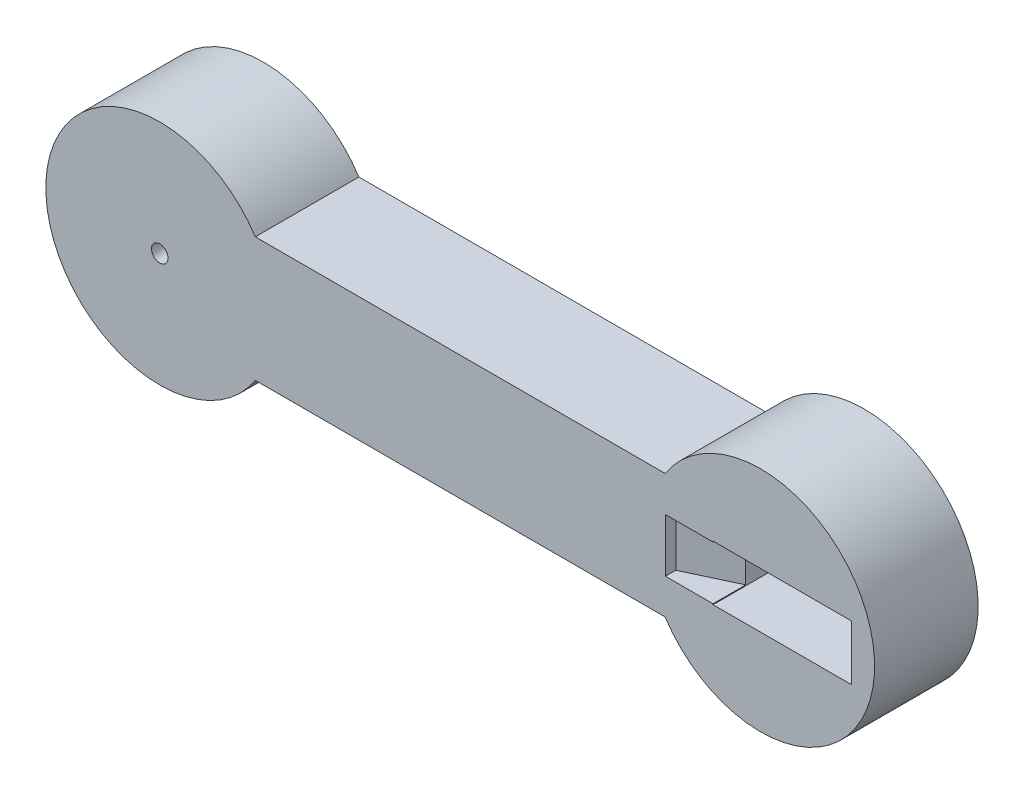
SolidWorks part; units mm, degrees
material "Custom Plastic"
ref_plane "Front Plane" through (0, 0, 0) normal (0, 0, 1) x (1, 0, 0)
ref_plane "Top Plane" through (0, 0, 0) normal (0, 1, 0) x (1, 0, 0)
ref_plane "Right Plane" through (0, 0, 0) normal (1, 0, 0) x (0, 0, -1)
sketch "Sketch1" plane through (0, 0, 0) normal (0, 0, 1) x (1, 0, 0)
  line L1 (0, 15) -> (145, 15)
  line L2 (0, 15) -> (0, -15)
  line L3 (0, -15) -> (145, -15)
  line L4 (145, 15) -> (145, -15)
  circle A0 centre (0, 0) radius 27.5
  circle A1 centre (145, 0) radius 27.5
  circle A2 centre (0, 0) radius 20
  point P9 (0, 0)
  dimension "D1" = 55
  dimension "D4" = 55
  dimension "D5" = 40
  dimension "D2" = 145
  dimension "D3" = 30
extrude "Boss-Extrude1" add sketch "Sketch1" along normal blind 25 contours L3 A1 L1 L4 | A1 L1 A0 L3 | L1 A1 L3 L4 | A2 L3 A0 L1 | A2 L1 A0 L3 | L3 A2 L1 L2 | L1 A2 L3 L2 region at (-6.7804, 0, 0) region at (9.0671, 0, 0) region at (-20.747, 0, 0) region at (21.8665, 0, 0) region at (72.5, 0, 0) region at (151.4116, 0, 0) region at (131.9332, 0, 0)
sketch "Sketch16" plane through (0, 0, 0) normal (0, 0, -1) x (-1, 0, 0)
  line L0 (-121.9511, -15) -> (-133.5193, -6.65) construction
  line L1 (-133.5193, -6.65) -> (-166.9193, -6.65)
  line L2 (-133.5193, -6.65) -> (-133.5193, 6.65)
  line L3 (-133.5193, 6.65) -> (-166.9193, 6.65)
  line L4 (-166.9193, -6.65) -> (-166.9193, 6.65)
  line L5 (-23.0489, -15) -> (-121.9511, -15) construction
  line L7 (-133.5193, 6.65) -> (-121.9511, 15) construction
  arc A1 (-121.9511, 15) -> (-121.9511, -15) centre (-145, 0) ccw construction
  dimension "D1" = 11.5682
  dimension "D2" = 33.4
  dimension "D3" = 13.3
extrude "Cut-Extrude10" cut sketch "Sketch16" against normal blind 4.5
ref_plane "Plane1" through (0, 0, 0) normal (0, -1, 0) x (-1, 0, 0)
sketch "Sketch19" plane through (0, 0, 0) normal (0, 0, -1) x (-1, 0, 0)
  circle A0 centre (0, 0) radius 20
extrude "Cut-Extrude14" cut sketch "Sketch19" against normal blind 5 contours A0
ref_plane "Plane2" through (0, 0, 6.5) normal (0, 0, -1) x (-1, 0, 0)
sketch "Sketch17" plane through (0, 0, 0) normal (0, 0, -1) x (-1, 0, 0)
  line L1 (-162.4193, 6.65) -> (-138.0193, 6.65)
  line L2 (-162.4193, 6.65) -> (-162.4193, -6.65)
  line L3 (-162.4193, -6.65) -> (-138.0193, -6.65)
  line L4 (-133.5193, -6.65) -> (-133.5193, 6.65)
  line L5 (-133.5193, 6.65) -> (-166.9193, 6.65)
  line L7 (-166.9193, -6.65) -> (-133.5193, -6.65)
  line L8 (-133.5193, -6.65) -> (-133.5193, 6.65)
  line L9 (-133.5193, 6.65) -> (-166.9193, 6.65)
  line L11 (-166.9193, -6.65) -> (-133.5193, -6.65)
  line L12 (-138.0193, 6.65) -> (-138.0193, -6.65)
  line L15 (-166.9193, 6.65) -> (-166.9193, -6.65)
  line L17 (-166.9193, 6.65) -> (-166.9193, -6.65)
  line M9 (-166.9193, 6.65) -> (-133.5193, 6.65)
  line M11 (-133.5193, -6.65) -> (-166.9193, -6.65)
  dimension "D2" = 4.5
  dimension "D3" = 4.5
  dimension "D1" = 0
extrude "Cut-Extrude11" cut sketch "Sketch17" against normal through all contours L12 L2 M9 M11 region at (150.2193, 0, 0)
sketch "Sketch18" plane through (0, 0, 0) normal (0, -1, 0) x (-1, 0, 0)
  line L0 (-138.0193, -25) -> (-138.0193, -15)
  line L6 (-122.0193, -25) -> (-122.0193, -22.5)
  line L8 (-166.9193, -4.5) -> (-162.4193, -4.5)
  line L9 (-166.9193, 0) -> (-166.9193, -4.5)
  line L11 (-166.9193, 0) -> (-166.9193, -4.5)
  line L13 (-133.5193, -4.5) -> (-133.5193, 0)
  line L14 (-133.5193, 0) -> (-166.9193, 0)
  line L16 (-166.9193, -4.5) -> (-162.4193, -4.5)
  line L21 (-133.5193, -4.5) -> (-133.5193, 0)
  line L22 (-133.5193, 0) -> (-166.9193, 0)
  line L26 (-122.0193, -22.5) -> (-138.0193, -15)
  line L28 (-23.0489, -25) -> (-121.9511, -25) construction
  line L30 (-138.0193, -25) -> (-122.0193, -25)
  line L31 (-138.0193, -15) -> (-138.0193, -25)
  line L34 (-162.4193, -25) -> (-138.0193, -25)
  line L35 (-162.4193, -25) -> (-138.0193, -25)
  line L36 (-138.0193, -25) -> (-138.0193, -4.5)
  line L37 (-138.0193, -25) -> (-138.0193, -4.5)
  line L38 (-162.4193, -4.5) -> (-162.4193, -25)
  line L40 (-162.4193, -4.5) -> (-162.4193, -25)
  line L42 (-138.0193, -4.5) -> (-133.5193, -4.5)
  line L43 (-138.0193, -4.5) -> (-133.5193, -4.5)
  dimension "D2" = 15
  dimension "D3" = 16
  dimension "D4" = 2.5
  dimension "D1" = 0
extrude "Cut-Extrude13" cut sketch "Sketch18" against normal mid plane 12.9 contours L0 region at (131.6193, 0, 21.5)
sketch "Sketch20" plane through (0, 0, 6.5) normal (0, 0, -1) x (-1, 0, 0)
  line L0 (-133.5193, 6.65) -> (-166.9193, 6.65) construction
  line L1 (-166.9193, 6.65) -> (-133.5193, 6.65)
  line L2 (-166.9193, 6.65) -> (-166.9193, -6.65)
  line L3 (-166.9193, -6.65) -> (-133.5193, -6.65)
  line L4 (-133.5193, 6.65) -> (-133.5193, -6.65)
  line L5 (-166.9193, 6.65) -> (-166.9193, -6.65) construction
  line L6 (-166.9193, -6.65) -> (-133.5193, -6.65) construction
  dimension "D1" = 33.4
extrude "Cut-Extrude15" cut sketch "Sketch20" against normal through all
sketch "Sketch21" plane through (0, 0, 0) normal (0, 0, -1) x (-1, 0, 0)
  circle A0 centre (-136.25, 0) radius 1.1
  circle A1 centre (-164.25, 0) radius 1.1
  dimension "D3" = 2.2
  dimension "D1" = 14.2989
  dimension "D2" = 28
extrude "Cut-Extrude16" cut sketch "Sketch21" against normal through all contours A1 | A0 region at (136.25, 0, 0) region at (164.25, 0, 0)
ref_axis "Axis1" through (136.25, 0, 34.2314) along (0, 0, -1)
sketch "Sketch22" plane through (0, 0, 25) normal (0, 0, 1) x (1, 0, 0)
  circle A0 centre (0, 0) radius 2
  arc A1 (23.0489, 15) -> (23.0489, -15) centre (0, 0) ccw construction
  dimension "D1" = 4
extrude "Cut-Extrude17" cut sketch "Sketch22" against normal up to surface (20 mm away) contours A0 region at (0, 0, 25) up to face at (-20, 0, 5)
ref_plane "Plane3" through (166.9193, -6.65, 0) normal (0, -1, 0) x (-1, 0, 0)
